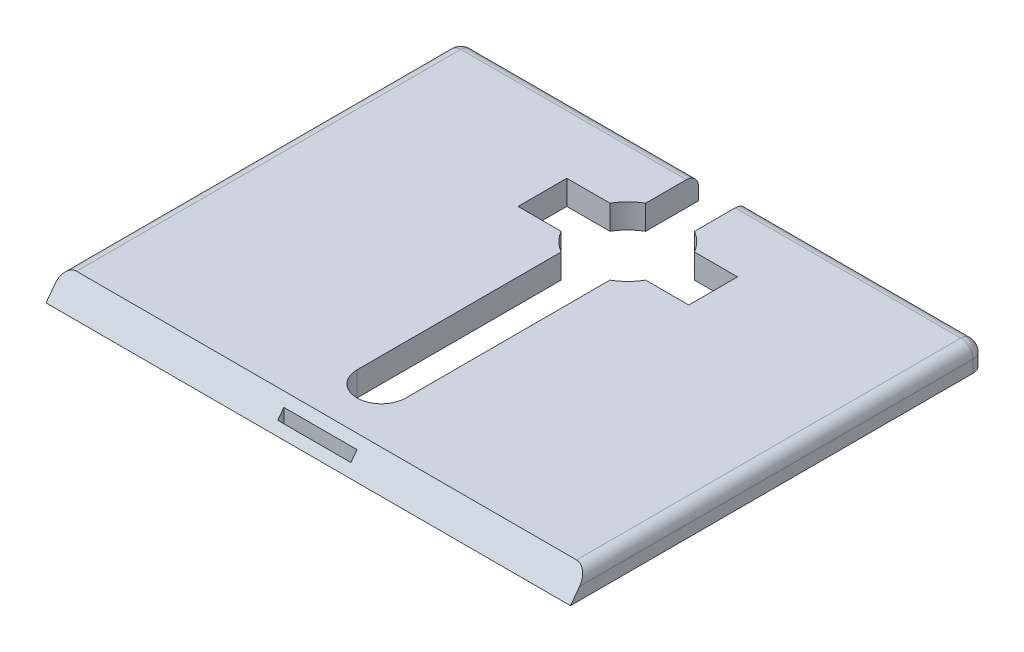
SolidWorks part; units mm, degrees
ref_plane "Ebene vorne" through (0, 0, 0) normal (0, 0, 1) x (1, 0, 0)
ref_plane "Ebene oben" through (0, 0, 0) normal (0, 1, 0) x (1, 0, 0)
ref_plane "Ebene rechts" through (0, 0, 0) normal (1, 0, 0) x (0, 0, -1)
sketch "Skizze1" plane through (0, 0, 0) normal (0, 1, 0) x (1, 0, 0)
  line L1 (-10.75, -8.5) -> (10.75, -8.5)
  line L2 (-10.75, -8.5) -> (-10.75, 8.5)
  line L3 (-10.75, 8.5) -> (10.75, 8.5)
  line L4 (10.75, -8.5) -> (10.75, 8.5)
  line L5 (-10.75, -8.5) -> (10.75, 8.5) construction
  line L6 (-10.75, 8.5) -> (10.75, -8.5) construction
  point P0 (0, 0)
  dimension "D1" = 17
  dimension "D2" = 21.5
extrude "Aufsatz-Linear austragen1" add sketch "Skizze1" along normal blind 1
fillet "Verrundung1" radius 0.5 3 edges at (10.75, 1, 0) (0, 1, -8.5) (-10.75, 1, 0)
sketch "Skizze2" plane through (-10.75, 0, 0) normal (-1, 0, 0) x (0, 0, 1)
  line L0 (8.5, 0) -> (7.75, 1)
  line L1 (-8, 1) -> (8.5, 1) construction
  line L2 (7.75, 1) -> (8.5, 1)
  line L3 (8.5, 1) -> (8.5, 0)
  dimension "D1" = 0.75
extrude "Schnitt-Linear austragen1" cut sketch "Skizze2" against normal up to surface (21.5 mm away) up to face at (10.75, 0.25, 0)
sketch "Skizze4" plane through (0, 1, 0) normal (0, 1, 0) x (1, 0, 0)
  line L6 (10.25, -7.75) -> (-10.25, -7.75) construction
  line L7 (-1.5, -8.25) -> (1.5, -8.25)
  line L8 (-1.5, -8.25) -> (-1.5, -8)
  line L9 (-1.5, -8) -> (1.5, -8)
  line L10 (1.5, -8.25) -> (1.5, -8)
  line L11 (-1.5, -8.25) -> (1.5, -8) construction
  line L12 (-1.5, -8) -> (1.5, -8.25) construction
  line L13 (-10.75, -8.125) -> (-10.75, -8.5) construction
  point P0 (0, -8.125)
  dimension "D1" = 0.25
  dimension "D2" = 0.25
  dimension "D3" = 3
  dimension "D4" = 10.75
extrude "Schnitt-Linear austragen2" cut sketch "Skizze4" against normal up to surface (1 mm away) up to face at (0, 0, 0)
fillet "Verrundung2" radius 0.5 4 edges at (10.6036, 0.8536, -8.3536) (-10.6036, 0.8536, -8.3536) (10.75, 0.25, -8.5) (-10.75, 0.25, -8.5)
sketch "Skizze5" plane through (0, 1, 0) normal (0, 1, 0) x (1, 0, 0)
  line L0 (-10.75, 8) -> (-10.75, -8.5) construction
  line L1 (-3.5, 3.6) -> (3.5, 3.6)
  line L2 (-3.5, 3.6) -> (-3.5, 5.6)
  line L3 (-3.5, 5.6) -> (3.5, 5.6)
  line L4 (3.5, 3.6) -> (3.5, 5.6)
  line L5 (-3.5, 3.6) -> (3.5, 5.6) construction
  line L6 (-3.5, 5.6) -> (3.5, 3.6) construction
  line L7 (-10.25, 8.5) -> (10.25, 8.5) construction
  circle A0 centre (0, 4.6) radius 2
  dimension "D2" = 4
  dimension "D1" = 7
  dimension "D3" = 2
  dimension "D4" = 10.75
  dimension "D5" = 3.9
extrude "Schlüsselloch" cut sketch "Skizze5" against normal up to surface (1 mm away) contours A0 L3 L2 L1 | L3 A0 | L1 A0 L3 | L1 A0 | A0 L1 L4 L3 region at (-2.7046, 1, -4.6) region at (0, 1, -4.6) region at (0, 1, -3.19) region at (2.7046, 1, -4.6) region at (0, 1, -6.01) up to face at (0, 0, 8.125)
sketch "Skizze6" plane through (0, 1, 0) normal (0, 1, 0) x (1, 0, 0)
  line L0 (0, 8.5) -> (0, -5.5) construction
  line L1 (-10.25, 8.5) -> (10.25, 8.5) construction
  line L2 (1, 8.5) -> (1, -5.5)
  line L3 (-1, 8.5) -> (-1, -5.5)
  line L5 (10.25, -7.75) -> (10.25, 8) construction
  arc A0 (1, 8.5) -> (-1, 8.5) centre (0, 8.5) ccw
  arc A1 (-1, -5.5) -> (1, -5.5) centre (0, -5.5) ccw
  point P4 (0, 1.5)
  dimension "D3" = 14
  dimension "D1" = 10.25
  dimension "D2" = 1
extrude "Langloch" cut sketch "Skizze6" against normal up to surface (1 mm away) up to face at (0, 0, -4.6)
